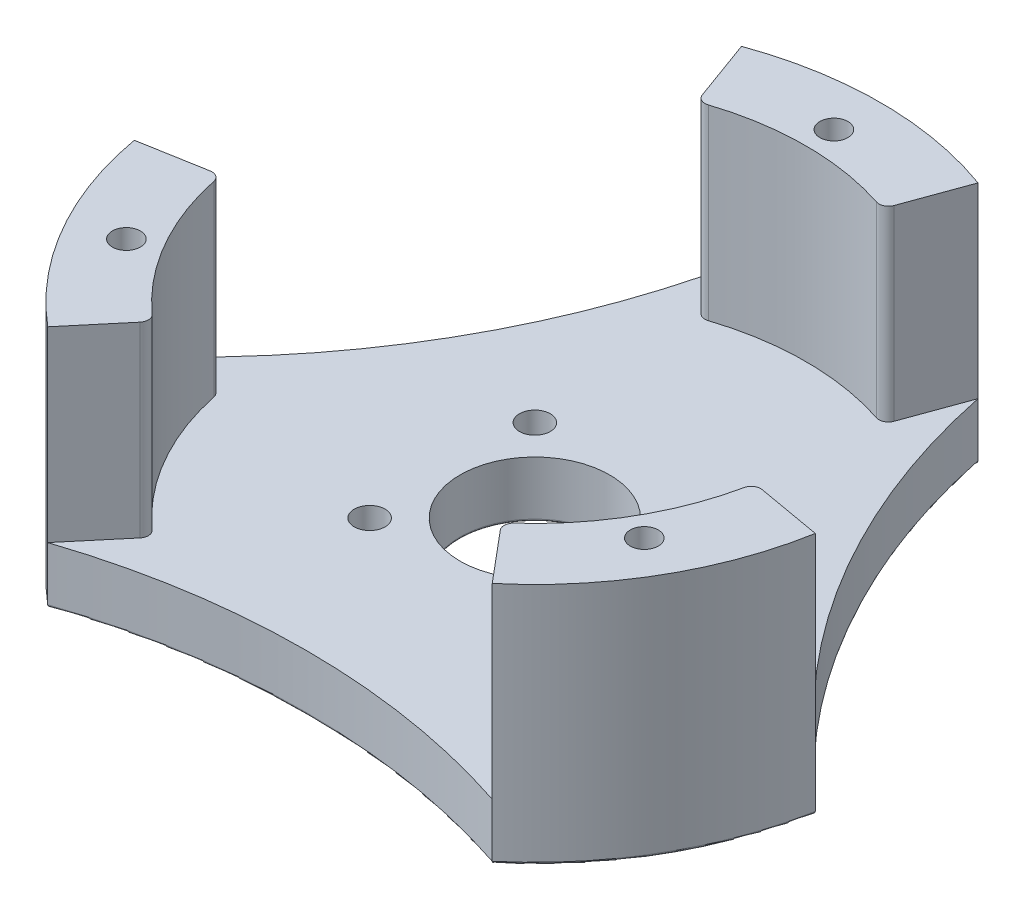
SolidWorks part; units mm, degrees
ref_plane "Front Plane" through (0, 0, 0) normal (0, 0, 1) x (1, 0, 0)
ref_plane "Top Plane" through (0, 0, 0) normal (0, 1, 0) x (1, 0, 0)
ref_plane "Right Plane" through (0, 0, 0) normal (1, 0, 0) x (0, 0, -1)
sketch "Sketch1" plane through (0, 0, 0) normal (0, 1, 0) x (1, 0, 0)
  line L1 (-8.8388, -8.8388) -> (8.8388, -8.8388) construction
  line L2 (-8.8388, -8.8388) -> (-8.8388, 8.8388) construction
  line L3 (-8.8388, 8.8388) -> (8.8388, 8.8388) construction
  line L4 (8.8388, -8.8388) -> (8.8388, 8.8388) construction
  line L5 (-8.8388, -8.8388) -> (8.8388, 8.8388) construction
  line L6 (-8.8388, 8.8388) -> (8.8388, -8.8388) construction
  circle A0 centre (0, 0) radius 37
  circle A1 centre (-8.8388, 8.8388) radius 1.65
  circle A2 centre (8.8388, 8.8388) radius 1.65
  circle A3 centre (8.8388, -8.8388) radius 1.65
  circle A4 centre (-8.8388, -8.8388) radius 1.65
  dimension "D1" = 74
  dimension "D4" = 3.3
  dimension "D2" = 12.5
extrude "Boss-Extrude1" add sketch "Sketch1" along normal blind 6
sketch "Sketch2" plane through (0, 6, 0) normal (0, 1, 0) x (1, 0, 0)
  line L0 (-12.6547, 34.7686) -> (0, 0) construction
  line L1 (0, 0) -> (12.6547, 34.7686) construction
  line L2 (0, -1000) -> (0, 49000) construction
  line L3 (-12.6547, 34.7686) -> (-9.9186, 27.2511)
  line L4 (9.9186, 27.2511) -> (12.6547, 34.7686)
  arc A0 (12.6547, 34.7686) -> (-12.6547, 34.7686) centre (0, 0) ccw
  circle A1 centre (0, 0) radius 37 construction
  arc A2 (9.9186, 27.2511) -> (-9.9186, 27.2511) centre (0, 0) ccw
  circle A3 centre (0, 32) radius 1.5
  dimension "D1" = 8
  dimension "D5" = 3
  dimension "D2" = 20
  dimension "D3" = 20
  dimension "D4" = 32
extrude "Boss-Extrude2" add sketch "Sketch2" along normal blind 20
sketch "Sketch16" plane through (0, 26, 0) normal (0, 1, 0) x (1, 0, 0)
  circle A0 centre (0, 32) radius 1.5
  circle A1 centre (0, 32) radius 1.5 construction
extrude "Cut-Extrude9" cut sketch "Sketch16" against normal through all
pattern_circular "CirPattern1" count 3 over 360 about axis through (0, 6, 0) along (0, -1, 0) of "Boss-Extrude2", "Cut-Extrude9" reverse direction yes
sketch "Sketch3" plane through (0, 6, 0) normal (0, 1, 0) x (1, 0, 0)
  circle A0 centre (0, 0) radius 8
  dimension "D1" = 16
extrude "Cut-Extrude1" cut sketch "Sketch3" against normal blind 10
sketch "Sketch4" plane through (0, 0, 0) normal (0, -1, 0) x (1, 0, 0)
  circle A0 centre (8.8388, 8.8388) radius 3.5
  circle A1 centre (8.8388, -8.8388) radius 3.5
  circle A2 centre (-8.8388, -8.8388) radius 3.5
  circle A3 centre (-8.8388, 8.8388) radius 3.5
  dimension "D1" = 7
extrude "Cut-Extrude2" cut sketch "Sketch4" against normal blind 3
sketch "Sketch5" plane through (0, 6, 0) normal (0, 1, 0) x (1, 0, 0)
  circle A1 centre (86.6025, 50) radius 75.5001
  dimension "D1" = 100
extrude "Cut-Extrude3" cut sketch "Sketch5" against normal through all
pattern_circular "CirPattern2" count 3 over 360 about axis through (0, 6, 0) along (0, -1, 0) of "Cut-Extrude3" reverse direction yes
fillet "Fillet1" radius 0.25 14 edges at (0, 0, 24.4999) (32.0429, 0, 18.5) (-32.0429, 0, 18.5) (0, 0, 8) (8.8388, 0, 5.3388) (8.8388, 0, -12.3388) (-8.8388, 0, -12.3388) (-8.8388, 0, 5.3388) (0, 0, -37) (21.2175, 0, -12.2499) (-21.2175, 0, -12.2499) (0, 0, -30.5) (26.4138, 0, 15.25) (-26.4138, 0, 15.25)
fillet "Fillet2" radius 1 6 edges at (28.5594, 16, 5.0358) (9.9186, 16, -27.2511) (-9.9186, 16, -27.2511) (18.6408, 16, 22.2153) (-28.5594, 16, 5.0358) (-18.6408, 16, 22.2153)
sketch "Sketch6" plane through (0, 26, 0) normal (0, 1, 0) x (1, 0, 0)
  line L0 (0, 32) -> (0, 0) construction
  line L1 (0, 0) -> (-27.7128, -16) construction
  line L2 (0, 0) -> (27.7128, -16) construction
  circle A0 centre (0, 0) radius 6
  circle A1 centre (15.5885, -9) radius 12
  circle A2 centre (0, 18) radius 12
  circle A3 centre (-15.5885, -9) radius 12
  point P7 (15.5885, -9)
  point P9 (0, 18)
  point P10 (-15.5885, -9)
  dimension "D1" = 12
  dimension "D2" = 24
sketch "Sketch7" plane through (0, 26, 0) normal (0, 1, 0) x (1, 0, 0)
  circle A0 centre (0, 0) radius 18
  circle A1 centre (0, 0) radius 13
  dimension "D1" = 26
  dimension "D2" = 5
ref_plane "Plane1" through (0, 21, 0) normal (0, 1, 0) x (1, 0, 0)
